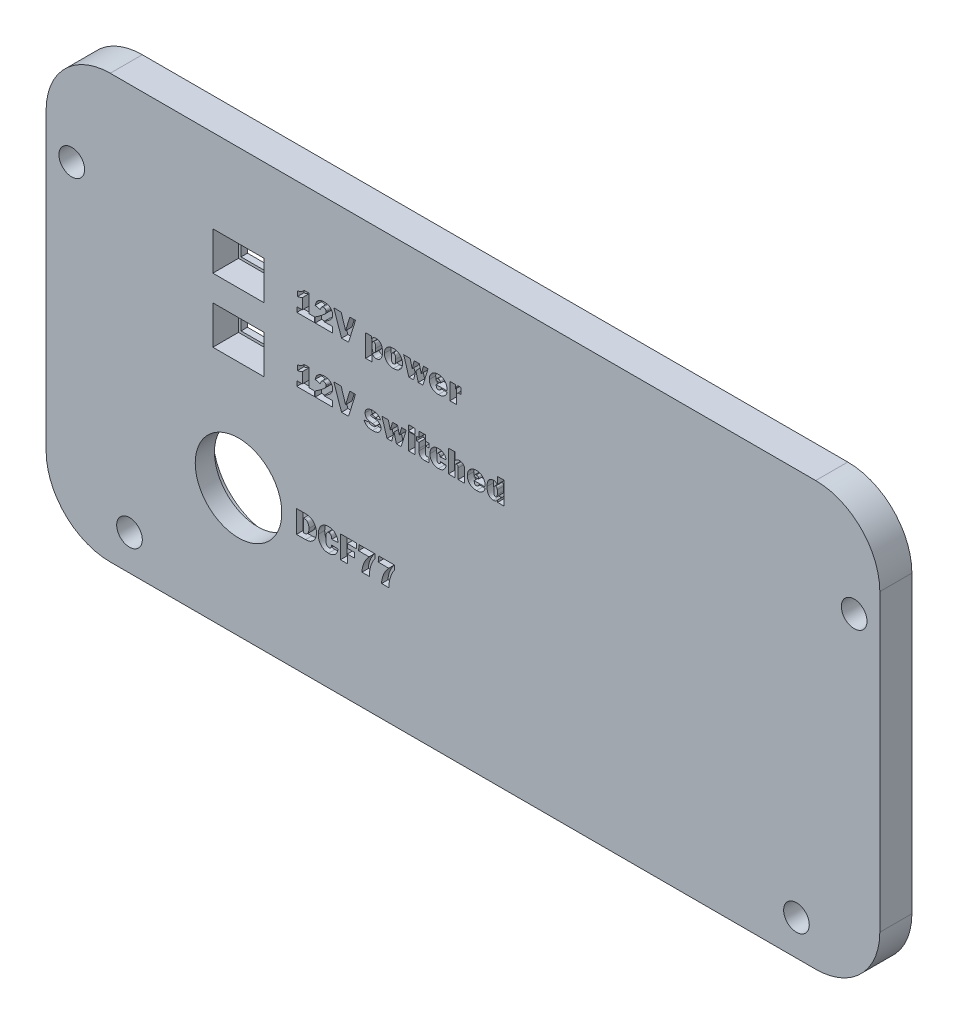
SolidWorks part; units mm, degrees
ref_plane "Front Plane" through (0, 0, 0) normal (0, 0, 1) x (1, 0, 0)
ref_plane "Top Plane" through (0, 0, 0) normal (0, 1, 0) x (1, 0, 0)
ref_plane "Right Plane" through (0, 0, 0) normal (1, 0, 0) x (0, 0, -1)
sketch "Sketch1" plane through (0, 0, 0) normal (0, 0, 1) x (1, 0, 0)
  line L0 (-55, 20) -> (55, -26) construction
  line L1 (-57, -25) -> (57, -25) construction
  line L2 (-57, -25) -> (-57, 25) construction
  line L3 (-57, 25) -> (57, 25) construction
  line L4 (57, -25) -> (57, 25) construction
  line L5 (-57, -25) -> (57, 25) construction
  line L6 (-57, 25) -> (57, -25) construction
  line L7 (-55, -36) -> (55, -36)
  line L8 (-65, -26) -> (-65, 20)
  line L9 (-55, 30) -> (55, 30)
  line L10 (65, -26) -> (65, 20)
  line L11 (55, 20) -> (-55, -26) construction
  line L12 (-62, -26) -> (-62, 20) construction
  line L13 (-55, 27) -> (55, 27) construction
  line L14 (62, -26) -> (62, 20) construction
  line L15 (-55, -33) -> (55, -33) construction
  line L16 (0, 0) -> (0, -3) construction
  line L17 (0, 25) -> (0, 30) construction
  line L18 (-62, -3) -> (-57, -3) construction
  arc A0 (55, 30) -> (65, 20) centre (55, 20) cw
  arc A1 (55, -36) -> (65, -26) centre (55, -26) ccw
  arc A2 (-55, -36) -> (-65, -26) centre (-55, -26) cw
  arc A3 (-65, 20) -> (-55, 30) centre (-55, 20) cw
  arc A4 (-55, -33) -> (-62, -26) centre (-55, -26) cw construction
  arc A5 (-62, 20) -> (-55, 27) centre (-55, 20) cw construction
  arc A6 (55, 27) -> (62, 20) centre (55, 20) cw construction
  arc A7 (55, -33) -> (62, -26) centre (55, -26) ccw construction
  point P0 (0, 0)
  point P6 (0, 0)
  dimension "D3" = 10
  dimension "D1" = 130
  dimension "D2" = 50
  dimension "D4" = 5
  dimension "D5" = 3
  dimension "D6" = 3
extrude "Boss-Extrude1" add sketch "Sketch1" along normal blind 5
sketch "Sketch2" plane through (0, 0, 0) normal (0, 0, -1) x (-1, 0, 0)
  line L1 (55, -36) -> (-55, -36) construction
  line L2 (65, 20) -> (65, -26) construction
  line L3 (-65, -25) -> (65, -25) construction
  line L4 (-65, -26) -> (-65, 20) construction
  circle A0 centre (35, -16) radius 6.75
  circle A1 centre (35, -16) radius 9 construction
  dimension "D1" = 13.5
  dimension "D3" = 18
  dimension "D2" = 30
  dimension "D4" = 11
extrude "Cut-Extrude1" cut sketch "Sketch2" against normal through all
sketch "Sketch3" plane through (0, 0, 0) normal (0, 0, -1) x (-1, 0, 0)
  line L0 (-39.5, 19) -> (20.5, 19) construction
  circle A0 centre (-39.5, 19) radius 1.25
  circle A1 centre (20.5, 19) radius 1.25
  circle A2 centre (-43.43, -14.1) radius 1.25
  circle A3 centre (9.5, -15) radius 1.25
  point P5 (-9.5, 19)
  dimension "D2" = 2.5
  dimension "D1" = 60
  dimension "D3" = 19
  dimension "D4" = 9.5
  dimension "D5" = 33.1
  dimension "D6" = 3.93
  dimension "D7" = 34
  dimension "D8" = 11
extrude "Cut-Extrude2" cut sketch "Sketch3" against normal offset from surface (3 mm away) 2 up to face at (-41.75, -16, 5)
sketch "Sketch6" plane through (0, 0, 0) normal (0, 0, -1) x (-1, 0, 0)
  circle A0 centre (35, -16) radius 9
  dimension "D1" = 18
extrude "Cut-Extrude4" cut sketch "Sketch6" against normal offset from surface (2 mm away) 3 up to face at (-41.75, -16, 5)
sketch "Sketch7" plane through (0, 0, 5) normal (0, 0, 1) x (1, 0, 0)
  line L0 (-35, 14) -> (-35, 4) construction
  line L1 (-39, 1) -> (-31, 1)
  line L2 (-39, 1) -> (-39, 7)
  line L3 (-39, 7) -> (-31, 7)
  line L4 (-31, 1) -> (-31, 7)
  line L5 (-39, 1) -> (-31, 7) construction
  line L6 (-39, 7) -> (-31, 1) construction
  line L7 (-39, 11) -> (-31, 11)
  line L8 (-39, 11) -> (-39, 17)
  line L9 (-39, 17) -> (-31, 17)
  line L10 (-31, 11) -> (-31, 17)
  line L11 (-39, 11) -> (-31, 17) construction
  line L12 (-39, 17) -> (-31, 11) construction
  line L13 (-35, 4) -> (-35, -16) construction
  point P0 (-35, 4)
  point P5 (-35, 14)
  point P12 (0, 0)
  point P14 (-40.5, -16)
  point P16 (0, 0)
  dimension "D1" = 8
  dimension "D2" = 6
  dimension "D3" = 20
  dimension "D4" = 10
extrude "Cut-Extrude5" cut sketch "Sketch7" against normal through all
sketch "Sketch8" plane through (0, 0, 5) normal (0, 0, 1) x (1, 0, 0)
  line L0 (-26.25, 12.25) -> (65, 12.25) construction
  line L2 (-26.25, 2.25) -> (65, 2.25) construction
  line L4 (-26.25, -17.75) -> (65, -17.75) construction
  line L5 (-31, 11) -> (-31, 17) construction
  line L7 (-31, 14) -> (-31, 12.25) construction
  line L8 (-31, 4) -> (-31, 2.25) construction
  line L9 (65, -26) -> (65, 20) construction
  line L10 (-28.25, -16) -> (-28.25, -17.75) construction
  line L11 (-28.25, -16) -> (-35, -16) construction
  line L12 (-31, 12.25) -> (-26.25, 12.25) construction
  line L13 (-31, 1) -> (-31, 7) construction
  line L14 (-31, 2.25) -> (-26.25, 2.25) construction
  line L15 (-26.25, -17.75) -> (-28.25, -17.75) construction
  line L16 (-26.25, 12.25) -> (-26.25, 2.25) construction
  line L17 (-26.25, 2.25) -> (-26.25, -17.75) construction
  circle A0 centre (-35, -16) radius 6.75 construction
  text T0 "12V power" font "Franklin Gothic Heavy" height 3.5
  text T1 "12V switched" font "Franklin Gothic Heavy" height 3.5
  text T2 "DCF77" font "Franklin Gothic Heavy" height 3.5
  point P2 (-33.75, -20.6926)
  point P3 (0, 0)
  point P6 (0, 0)
  point P16 (-31, 14)
  dimension "D1" = 1.75
  dimension "D2" = 2
extrude "Cut-Extrude6" cut sketch "Sketch8" against normal blind 1
sketch "Sketch9" plane through (0, 0, 0) normal (0, 0, -1) x (-1, 0, 0)
  line L0 (39, 7) -> (39, 1) construction
  line L1 (39, 1) -> (31, 1) construction
  line L2 (31, 1) -> (31, 7) construction
  line L3 (31, 7) -> (39, 7) construction
  line L4 (31, 17) -> (39, 17) construction
  line L5 (39, 17) -> (39, 11) construction
  line L6 (39, 11) -> (31, 11) construction
  line L7 (31, 11) -> (31, 17) construction
  line L8 (39, 7) -> (39, 1)
  line L9 (39, 1) -> (31, 1)
  line L10 (31, 1) -> (31, 7)
  line L11 (31, 7) -> (39, 7)
  line L12 (31, 17) -> (39, 17)
  line L13 (39, 17) -> (39, 11)
  line L14 (39, 11) -> (31, 11)
  line L15 (31, 11) -> (31, 17)
  line L16 (31.4, 16.6) -> (38.6, 16.6)
  line L17 (38.6, 16.6) -> (38.6, 11.4)
  line L18 (38.6, 11.4) -> (31.4, 11.4)
  line L19 (31.4, 11.4) -> (31.4, 16.6)
  line L20 (38.6, 6.6) -> (38.6, 1.4)
  line L21 (38.6, 1.4) -> (31.4, 1.4)
  line L22 (31.4, 1.4) -> (31.4, 6.6)
  line L23 (31.4, 6.6) -> (38.6, 6.6)
  line L24 (35, 16.6) -> (35, 17) construction
  line L25 (35, 6.6) -> (35, 7) construction
  dimension "D1" = 0.4
extrude "Boss-Extrude2" add sketch "Sketch9" against normal blind 1
sketch "Sketch10" plane through (0, 0, 0) normal (0, 0, -1) x (-1, 0, 0)
  circle A0 centre (-43.43, -14.1) radius 1.25 construction
  circle A1 centre (9.5, -15) radius 1.25 construction
  circle A2 centre (20.5, 19) radius 1.25 construction
  circle A3 centre (-39.5, 19) radius 1.25 construction
  circle A4 centre (-43.43, -14.1) radius 1.25
  circle A5 centre (9.5, -15) radius 1.25
  circle A6 centre (20.5, 19) radius 1.25
  circle A7 centre (-39.5, 19) radius 1.25
  circle A8 centre (-39.5, 19) radius 3.25
  circle A9 centre (20.5, 19) radius 3.25
  circle A10 centre (9.5, -15) radius 3.25
  circle A11 centre (-43.43, -14.1) radius 3.25
  dimension "D1" = 2
extrude "Boss-Extrude3" add sketch "Sketch10" along normal blind 5
sketch "Sketch11" plane through (0, 0, 0) normal (0, 0, -1) x (-1, 0, 0)
  line L0 (55, -36) -> (-55, -36) construction
  line L1 (-45.55, 5.71) -> (-35.55, 5.71)
  line L2 (-45.55, 5.71) -> (-45.55, -4.29)
  line L3 (-45.55, -4.29) -> (-35.55, -4.29)
  line L4 (-35.55, 5.71) -> (-35.55, -4.29)
  line L5 (-45.55, 5.71) -> (-35.55, -4.29) construction
  line L6 (-45.55, -4.29) -> (-35.55, 5.71) construction
  line L7 (-65, -26) -> (-65, 20) construction
  point P0 (-40.55, 0.71)
  dimension "D1" = 36.71
  dimension "D2" = 10
  dimension "D3" = 24.45
extrude "Cut-Extrude7" cut sketch "Sketch11" against normal blind 3
fillet "Fillet1" radius 1 8 edges at (40.55, -4.29, 3) (45.55, 0.71, 3) (40.55, 5.71, 3) (35.55, 0.71, 3) (45.55, -4.29, 1.5) (35.55, -4.29, 1.5) (35.55, 5.71, 1.5) (45.55, 5.71, 1.5)
sketch "Sketch12" plane through (0, 0, 5) normal (0, 0, 1) x (1, 0, 0)
  line L0 (-61, -30.5) -> (-52, -30.5) construction
  line L5 (0, 15) -> (0, -30.5) construction
  line L6 (-61, 15) -> (61, 15) construction
  line L7 (-61, 15) -> (-61, -30.5) construction
  line L8 (-61, -30.5) -> (61, -30.5) construction
  line L9 (61, 15) -> (61, -30.5) construction
  line L10 (55, 30) -> (-55, 30) construction
  line L11 (-55, -36) -> (55, -36) construction
  line L12 (-65, 20) -> (-65, -26) construction
  line L13 (52, -30.5) -> (61, -30.5) construction
  circle A0 centre (-61, 15) radius 2
  circle A1 centre (61, 15) radius 2
  circle A2 centre (52, -30.5) radius 2
  circle A3 centre (-52, -30.5) radius 2
  dimension "D4" = 4
  dimension "D1" = 15
  dimension "D2" = 5.5
  dimension "D3" = 4
  dimension "D5" = 9
extrude "Cut-Extrude8" cut sketch "Sketch12" against normal through all
